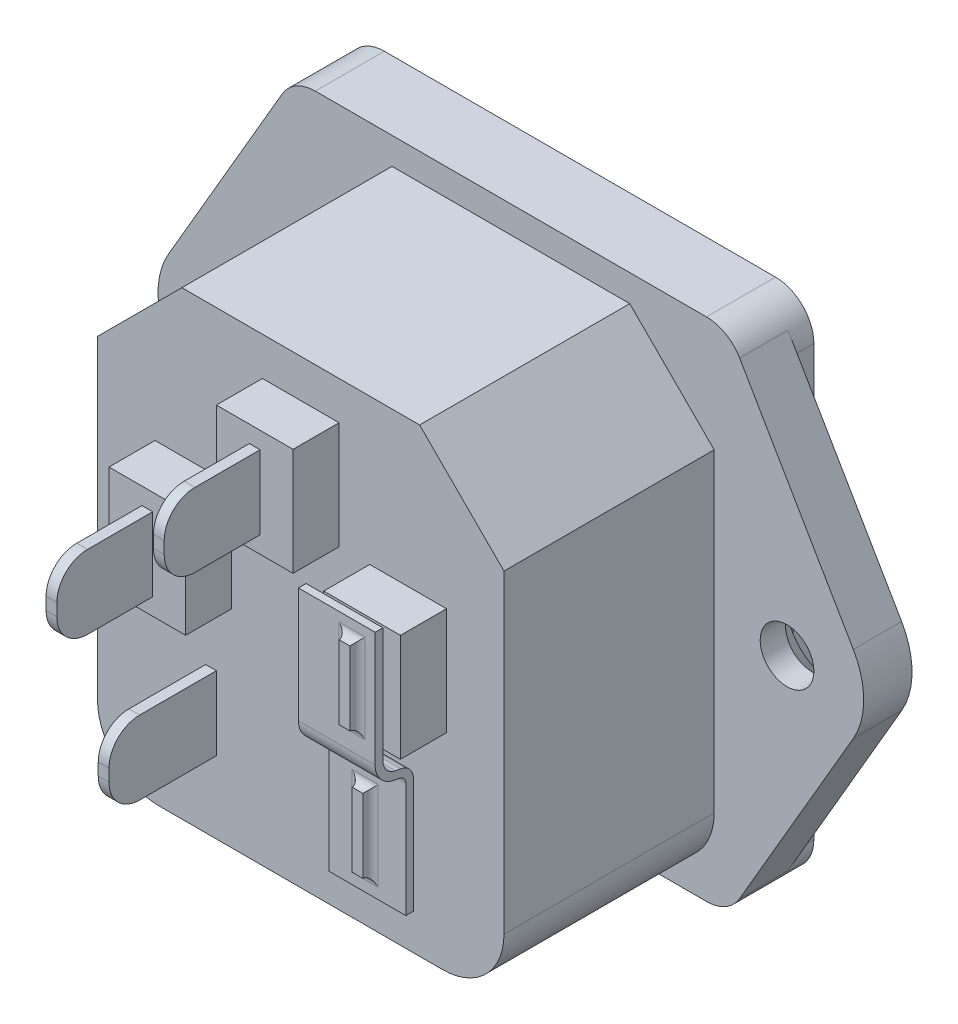
SolidWorks part; units mm, degrees
material "PA Type 6"
ref_plane "Front Plane" through (0, 0, 0) normal (0, 0, 1) x (1, 0, 0)
ref_plane "Top Plane" through (0, 0, 0) normal (0, 1, 0) x (1, 0, 0)
ref_plane "Right Plane" through (0, 0, 0) normal (1, 0, 0) x (0, 0, -1)
sketch "Sketch1" plane through (0, 0, 0) normal (0, 0, 1) x (1, 0, 0)
  line L0 (55, 0) -> (-55, 0) construction
  line L1 (0, -55) -> (0, 55) construction
  line L2 (-12.75, 11.25) -> (12.75, 11.25)
  line L3 (-12.75, -21.75) -> (12.75, -21.75)
  line L5 (-14.9111, 10.0068) -> (-22.3222, -2.7363)
  line L7 (-22.3222, -7.7637) -> (-14.9111, -20.5068)
  line L8 (22.3222, -7.7637) -> (14.9111, -20.5068)
  line L9 (14.9111, 10.0068) -> (22.3222, -2.7363)
  circle A0 centre (-18, -5.25) radius 1.75
  circle A1 centre (18, -5.25) radius 1.75
  arc A2 (-22.3222, -2.7363) -> (-22.3222, -7.7637) centre (-18, -5.25) ccw
  arc A3 (22.3222, -7.7637) -> (22.3222, -2.7363) centre (18, -5.25) ccw
  arc A4 (-12.75, 11.25) -> (-14.9111, 10.0068) centre (-12.75, 8.75) ccw
  arc A5 (12.75, 11.25) -> (14.9111, 10.0068) centre (12.75, 8.75) cw
  arc A6 (14.9111, -20.5068) -> (12.75, -21.75) centre (12.75, -19.25) cw
  arc A7 (-14.9111, -20.5068) -> (-12.75, -21.75) centre (-12.75, -19.25) ccw
  dimension "D3" = 3.5
  dimension "D8" = 2.5
  dimension "D9" = 10
  dimension "D1" = 36
  dimension "D2" = 18
  dimension "D4" = 33
  dimension "D5" = 11.25
  dimension "D6" = 25.5
  dimension "D7" = 12.75
  dimension "D10" = 16.5
extrude "Extrude1" add sketch "Sketch1" along normal blind 3.15
chamfer "Chamfer1" distance 1.5 angle 45 2 edges at (19.75, -5.25, 0) (-16.25, -5.25, 0)
sketch "Sketch2" plane through (0, 0, 0) normal (0, 0, -1) x (-1, 0, 0)
  line L0 (-12.75, 11.25) -> (12.75, 11.25)
  line L1 (-12.75, 11.25) -> (12.75, 11.25) construction
  line L2 (-15.25, 8.75) -> (-15.25, -19.25)
  line L3 (-12.75, -21.75) -> (12.75, -21.75)
  line L4 (12.75, -21.75) -> (-12.75, -21.75) construction
  line L5 (15.25, -19.25) -> (15.25, 8.75)
  arc A0 (-12.75, 11.25) -> (-15.25, 8.75) centre (-12.75, 8.75) ccw
  arc A1 (-12.75, 11.25) -> (-14.9111, 10.0068) centre (-12.75, 8.75) ccw construction
  arc A2 (-15.25, -19.25) -> (-12.75, -21.75) centre (-12.75, -19.25) ccw
  arc A3 (12.75, -21.75) -> (14.9111, -20.5068) centre (12.75, -19.25) ccw construction
  arc A4 (12.75, -21.75) -> (15.25, -19.25) centre (12.75, -19.25) ccw
  arc A5 (15.25, 8.75) -> (12.75, 11.25) centre (12.75, 8.75) ccw
  arc A6 (14.9111, 10.0068) -> (12.75, 11.25) centre (12.75, 8.75) ccw construction
  arc A7 (-14.9111, -20.5068) -> (-12.75, -21.75) centre (-12.75, -19.25) ccw construction
extrude "Extrude2" add sketch "Sketch2" along normal blind 1.35
sketch "Sketch3" plane through (0, 0, 3.15) normal (0, 0, 1) x (1, 0, 0)
  line L0 (-7.75, 9.5) -> (7.75, 9.5)
  line L1 (7.75, 9.5) -> (13.25, 4)
  line L2 (13.25, 4) -> (13.25, -16.5)
  line L3 (9.25, -20.5) -> (-9.25, -20.5)
  line L4 (-13.25, -16.5) -> (-13.25, 4)
  line L5 (-13.25, 4) -> (-7.75, 9.5)
  line L6 (2.475, 0) -> (-2.475, 0) construction
  line L7 (0, -2.475) -> (0, 2.475) construction
  arc A0 (13.25, -16.5) -> (9.25, -20.5) centre (9.25, -16.5) cw
  arc A1 (-13.25, -16.5) -> (-9.25, -20.5) centre (-9.25, -16.5) ccw
  dimension "D1" = 4
  dimension "D2" = 26.5
  dimension "D3" = 30
  dimension "D4" = 9.5
  dimension "D5" = 13.25
  dimension "D6" = 5.5
extrude "Extrude3" add sketch "Sketch3" along normal blind 13.7
sketch "Sketch4" plane through (0, 0, 16.85) normal (0, 0, 1) x (1, 0, 0)
  line L0 (-9.5, 0) -> (-4.5, 0)
  line L1 (-2.5, 0) -> (-2.5, 7)
  line L2 (-2.5, 7) -> (2.5, 7)
  line L3 (2.5, 7) -> (2.5, 0)
  line L4 (9.5, 0) -> (4.5, 0)
  line L5 (9.5, 0) -> (9.5, -7)
  line L6 (9.5, -7) -> (4.5, -7)
  line L7 (4.5, -7) -> (4.5, 0)
  line L8 (-2.5, 0) -> (2.5, 0)
  line L9 (-4.5, 0) -> (-4.5, -7)
  line L10 (-4.5, -7) -> (-9.5, -7)
  line L11 (-9.5, -7) -> (-9.5, 0)
  line L16 (0, -10.01) -> (0, 10.01) construction
  line L19 (10.01, 0) -> (-10.01, 0) construction
  dimension "D3" = 7
  dimension "D4" = 19
  dimension "D5" = 5
  dimension "D6" = 5
  dimension "D7" = 4.5
  dimension "D8" = 5
  dimension "D9" = 2.5
  dimension "D10" = 7
extrude "Extrude4" add sketch "Sketch4" along normal blind 3
sketch "Sketch5" plane through (0, 0, 19.85) normal (0, 0, 1) x (1, 0, 0)
  line L1 (0, -11.66) -> (0, 11.66) construction
  line L2 (-0.35, 5.9) -> (0.35, 5.9)
  line L3 (-0.35, 5.9) -> (-0.35, 1.1)
  line L4 (-0.35, 1.1) -> (0.35, 1.1)
  line L5 (0.35, 5.9) -> (0.35, 1.1)
  line L6 (6.65, -1.1) -> (7.35, -1.1)
  line L7 (6.65, -1.1) -> (6.65, -5.9)
  line L8 (6.65, -5.9) -> (7.35, -5.9)
  line L9 (7.35, -1.1) -> (7.35, -5.9)
  line L10 (-7.35, -1.1) -> (-6.65, -1.1)
  line L11 (-7.35, -1.1) -> (-7.35, -5.9)
  line L12 (-7.35, -5.9) -> (-6.65, -5.9)
  line L13 (-6.65, -1.1) -> (-6.65, -5.9)
  line L14 (11.66, 0) -> (-11.66, 0) construction
  line L15 (-4.5, -7) -> (-4.5, 0) construction
  line L16 (-9.5, 0) -> (-9.5, -7) construction
  dimension "D1" = 4.8
  dimension "D2" = 0.7
  dimension "D3" = 0.35
  dimension "D4" = 1.1
  dimension "D5" = 1.1
  dimension "D6" = 6.65
  dimension "D7" = 2.15
  dimension "D8" = 2.15
  dimension "D9" = 6.65
extrude "Extrude5" add sketch "Sketch5" along normal blind 6.25
sketch "Sketch6" plane through (0, 0, -1.35) normal (0, 0, -1) x (-1, 0, 0)
  line L0 (-6.7, 7.85) -> (6.7, 7.85)
  line L1 (6.7, 7.85) -> (12.2, 2.35)
  line L2 (12.2, 2.35) -> (12.2, -5.35)
  line L3 (-6.7, 7.85) -> (-12.2, 2.35)
  line L4 (-12.2, 2.35) -> (-12.2, -5.35)
  line L5 (-9.7, -7.85) -> (9.7, -7.85)
  line L6 (15.0975, 0) -> (-15.0975, 0) construction
  line L7 (0, 15.0975) -> (0, -15.0975) construction
  arc A0 (9.7, -7.85) -> (12.2, -5.35) centre (9.7, -5.35) ccw
  arc A1 (-12.2, -5.35) -> (-9.7, -7.85) centre (-9.7, -5.35) ccw
  dimension "D1" = 2.5
  dimension "D2" = 15.7
  dimension "D3" = 7.85
  dimension "D4" = 24.4
  dimension "D5" = 12.2
  dimension "D6" = 5.5
extrude "Extrude6" cut sketch "Sketch6" against normal blind 17
fillet "Fillet1" radius 0.5 8 edges at (-12.2, -1.5, -1.35) (-11.4678, -7.1178, -1.35) (0, -7.85, -1.35) (11.4678, -7.1178, -1.35) (-9.45, 5.1, -1.35) (0, 7.85, -1.35) (12.2, -1.5, -1.35) (9.45, 5.1, -1.35)
sketch "Sketch7" plane through (0, 0, 15.65) normal (0, 0, -1) x (-1, 0, 0)
  line L0 (15.0975, 0) -> (-15.0975, 0) construction
  line L1 (-8, 0) -> (-6, 0)
  line L2 (-8, 0) -> (-8, -4)
  line L3 (-8, -4) -> (-6, -4)
  line L4 (-6, 0) -> (-6, -4)
  line L7 (6, 0) -> (8, 0)
  line L8 (6, 0) -> (6, -4)
  line L9 (6, -4) -> (8, -4)
  line L10 (8, 0) -> (8, -4)
  line L11 (0, 15.0975) -> (0, -15.0975) construction
  dimension "D1" = 2
  dimension "D2" = 12
  dimension "D3" = 4
  dimension "D4" = 4
  dimension "D5" = 6
extrude "Extrude7" add sketch "Sketch7" along normal blind 14
sketch "Sketch8" plane through (0, 0, 15.65) normal (0, 0, -1) x (-1, 0, 0)
  line L0 (15.0975, 0) -> (-15.0975, 0) construction
  line L1 (-1, 4) -> (1, 4)
  line L2 (-1, 4) -> (-1, 0)
  line L3 (-1, 0) -> (1, 0)
  line L4 (1, 4) -> (1, 0)
  line L5 (0, 15.0975) -> (0, -15.0975) construction
  dimension "D1" = 4
  dimension "D2" = 2
  dimension "D3" = 1
extrude "Extrude8" add sketch "Sketch8" along normal blind 16.5
chamfer "Chamfer3" distance 0.75 angle 45 12 edges at (1, 2, -0.85) (0, 0, -0.85) (-1, 2, -0.85) (0, 4, -0.85) (-6, -2, 1.65) (-7, -4, 1.65) (-8, -2, 1.65) (-7, 0, 1.65) (7, 0, 1.65) (8, -2, 1.65) (7, -4, 1.65) (6, -2, 1.65)
sketch "Sketch9" plane through (0, 0, 16.85) normal (0, 0, 1) x (1, 0, 0)
  line L1 (-6.2, -11) -> (-5.5, -11)
  line L2 (-6.2, -11) -> (-6.2, -15.8)
  line L3 (-6.2, -15.8) -> (-5.5, -15.8)
  line L4 (-5.5, -11) -> (-5.5, -15.8)
  line L6 (0, -15.0975) -> (0, 15.0975) construction
  line L8 (15.0975, 0) -> (-15.0975, 0) construction
  line L10 (5.5, -11) -> (6.2, -11)
  line L11 (5.5, -11) -> (5.5, -15.8)
  line L12 (5.5, -15.8) -> (6.2, -15.8)
  line L13 (6.2, -11) -> (6.2, -15.8)
  dimension "D1" = 0.7
  dimension "D2" = 4.8
  dimension "D3" = 5.5
  dimension "D4" = 11
  dimension "D5" = 5.5
extrude "Extrude9" add sketch "Sketch9" along normal blind 7
fillet "Fillet2" radius 2 10 edges at (5.85, -11, 23.85) (7, -5.9, 26.1) (7, -1.1, 26.1) (0, 5.9, 26.1) (0, 1.1, 26.1) (-7, -1.1, 26.1) (-7, -5.9, 26.1) (-5.85, -11, 23.85) (-5.85, -15.8, 23.85) (5.85, -15.8, 23.85)
ref_plane "Plane1" through (6, 0, 0) normal (1, 0, 0) x (0, 0, -1)
sketch "Sketch10" plane through (6, 0, 0) normal (1, 0, 0) x (0, 0, -1)
  line L0 (-20, 0) -> (-20, -7.5)
  line L1 (15.0975, 0) -> (-15.0975, 0) construction
  line L2 (-19.1736, -8.4848) -> (-18.8264, -8.546)
  line L3 (-18, -9.5309) -> (-18, -17)
  line L4 (0, 18.15) -> (0, -18.15) construction
  arc A0 (-18, -9.5309) -> (-18.8264, -8.546) centre (-19, -9.5309) ccw
  arc A1 (-20, -7.5) -> (-19.1736, -8.4848) centre (-19, -7.5) ccw
  dimension "D3" = 1
  dimension "D1" = 2
  dimension "D2" = 20
  dimension "D4" = 7.5
  dimension "D5" = 10
  dimension "D6" = 17
extrude "Extrude-Thin1" add sketch "Sketch10" along normal mid plane 5 thin thin type one direction wall 0.5
sketch "Sketch12" plane through (7.35, 0, 0) normal (1, 0, 0) x (0, 0, -1)
  line L0 (-21, -1.1) -> (-21, -10.0281)
  line L1 (-24.1, -1.1) -> (-20.5, -1.1) construction
  line L3 (-19, -16.1) -> (-27, -16.1)
  line L4 (-27, -16.1) -> (-27, -1.1)
  line L5 (-27, -1.1) -> (-21, -1.1)
  line L6 (0, 18.15) -> (0, -18.15) construction
  line L7 (-21, -10.0281) -> (-19, -10.0281)
  line L8 (-19, -10.0281) -> (-19, -16.1)
  dimension "D1" = 27
  dimension "D2" = 6
  dimension "D3" = 15
  dimension "D4" = 2
extrude "Extrude10" cut sketch "Sketch12" against normal blind 2
fillet "Fillet3" radius 0.5 4 edges at (5.85, -11, 18.5) (5.5, -13.4, 18.5) (5.85, -15.8, 18.5) (6.2, -13.4, 18.5)
fillet "Fillet4" radius 0.5 4 edges at (7, -1.1, 20.5) (6.65, -3.5, 20.5) (7, -5.9, 20.5) (7.35, -3.5, 20.5)
sketch "Sketch13" plane through (0, 0, -1.35) normal (0, 0, -1) x (-1, 0, 0)
  line L0 (0, 15.0975) -> (0, -15.0975) construction
  line L1 (-12.25, -10) -> (12.25, -10)
  line L2 (-12.25, -10) -> (-12.25, -18.5)
  line L3 (-12.25, -18.5) -> (12.25, -18.5)
  line L4 (12.25, -10) -> (12.25, -18.5)
  line L6 (15.0975, 0) -> (-15.0975, 0) construction
  dimension "D1" = 8.5
  dimension "D2" = 24.5
  dimension "D3" = 12.25
  dimension "D4" = 10
extrude "Extrude11" add sketch "Sketch13" along normal blind 0.5
